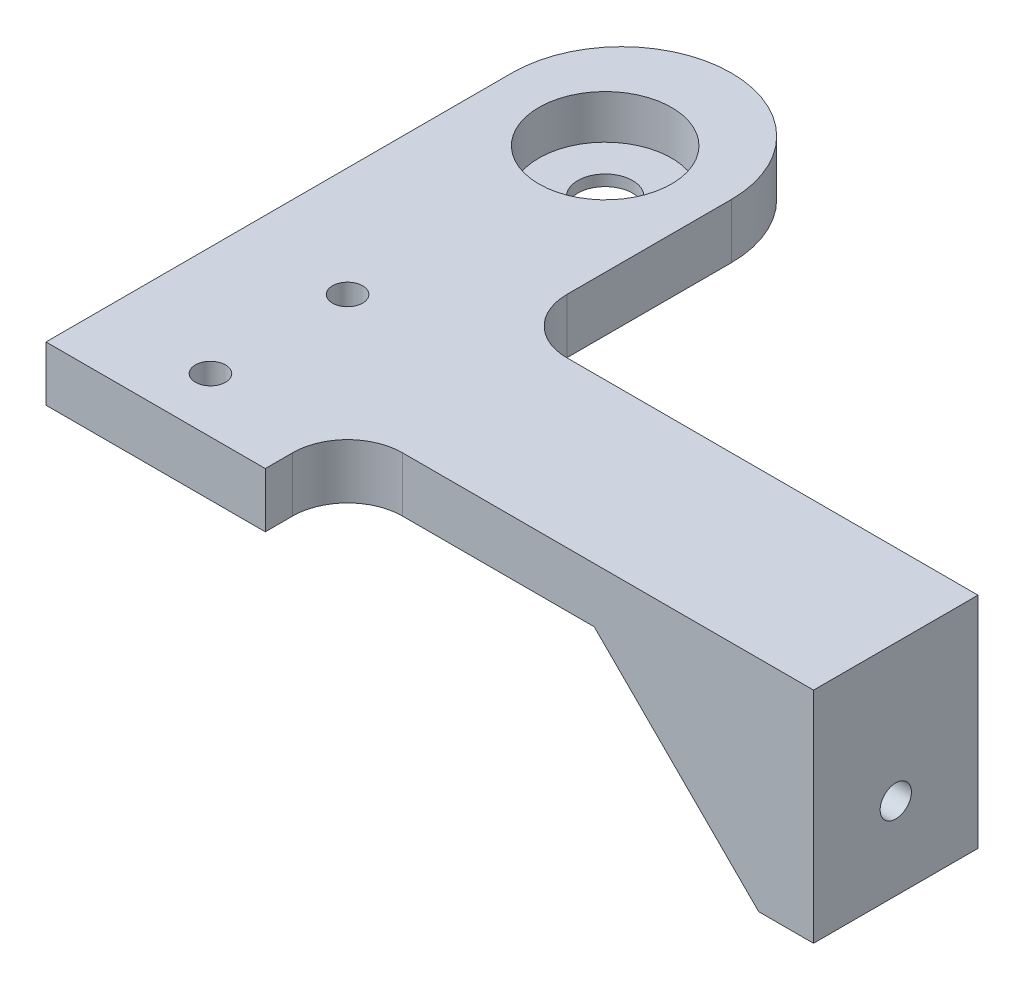
SolidWorks part; units mm, degrees
ref_plane "Front Plane" through (0, 0, 0) normal (0, 0, 1) x (1, 0, 0)
ref_plane "Top Plane" through (0, 0, 0) normal (0, 1, 0) x (1, 0, 0)
ref_plane "Right Plane" through (0, 0, 0) normal (1, 0, 0) x (0, 0, -1)
sketch "Sketch1" plane through (0, 0, 0) normal (0, 1, 0) x (1, 0, 0)
  line L1 (-20, 0) -> (20, 0)
  line L6 (-20, 85) -> (-20, 0)
  line L7 (20, 85) -> (20, 0)
  circle A2 centre (0, 10) radius 2.75
  circle A6 centre (0, 82) radius 12.1
  circle A7 centre (0, 35) radius 2.75
  arc A10 (-20, 85) -> (20, 85) centre (0, 85) cw
  point P0 (0, 0)
  dimension "D2" = 5.5
  dimension "D3" = 20
  dimension "D5" = 5.5
  dimension "D6" = 24.2
  dimension "D9" = 0
  dimension "D8" = 3
  dimension "D1" = 40
  dimension "D7" = 10
  dimension "D4" = 25
  dimension "D10" = 47
extrude "Boss-Extrude1" add sketch "Sketch1" along normal blind 8
ref_plane "Plane1" through (0, 0, -30) normal (0, 0, 1) x (1, 0, 0)
sketch "Sketch7" plane through (0, 0, 0) normal (0, -1, 0) x (1, 0, 0)
  line L1 (20, 0) -> (20, -85)
  line L2 (-20, -85) -> (-20, 0)
  line L3 (20, 0) -> (-20, 0)
  circle A0 centre (0, -82) radius 5
  arc A1 (20, -85) -> (-20, -85) centre (0, -85) cw
  circle A2 centre (0, -10) radius 2.75
  circle A3 centre (0, -35) radius 2.75
  dimension "D1" = 10
extrude "Boss-Extrude5" add sketch "Sketch7" along normal blind 2
sketch "Sketch8" plane through (0, 0, -30) normal (0, 0, 1) x (1, 0, 0)
  line L5 (105, 8) -> (20, 8)
  line L6 (20, 8) -> (20, -2)
  line L7 (105, 8) -> (105, -32)
  line L8 (105, -32) -> (95, -32)
  line L10 (91.4645, -2) -> (20, -2)
  line L11 (91.4645, -2) -> (95, -5.5355)
  line L12 (95, -5.5355) -> (95, -32)
  dimension "D1" = 85
  dimension "D2" = 40
  dimension "D3" = 5
  dimension "D4" = 135
  dimension "D5" = 10
extrude "Boss-Extrude6" add sketch "Sketch8" along normal mid plane 30
sketch "Sketch9" plane through (105, 0, 0) normal (1, 0, 0) x (0, 0, -1)
  line L0 (15, -32) -> (45, -32) construction
  circle A0 centre (30, -17) radius 2.85
  dimension "D1" = 5.7
  dimension "D2" = 15
extrude "Cut-Extrude2" cut sketch "Sketch9" against normal blind 40
fillet "Fillet2" radius 10 2 edges at (20, 3, -15) (20, 3, -45)
sketch "Sketch10" plane through (0, 0, -45) normal (0, 0, -1) x (-1, 0, 0)
  line L0 (-95, -32) -> (-95, -2)
  line L1 (-95, -5.5355) -> (-95, -32) construction
  line L2 (-95, -2) -> (-65, -2)
  line L3 (-30, -2) -> (-91.4645, -2) construction
  line L4 (-65, -2) -> (-95, -32)
  dimension "D1" = 45
  dimension "D2" = 90
  dimension "D3" = 30
extrude "Boss-Extrude7" add sketch "Sketch10" against normal blind 5
mirror "Mirror1" about plane through (0, 0, -30) normal (0, 0, 1) of "Boss-Extrude7"
chamfer "Chamfer1" distance 2.5 angle 45 2 edges at (0, -2, -12.75) (0, -2, -37.75)
